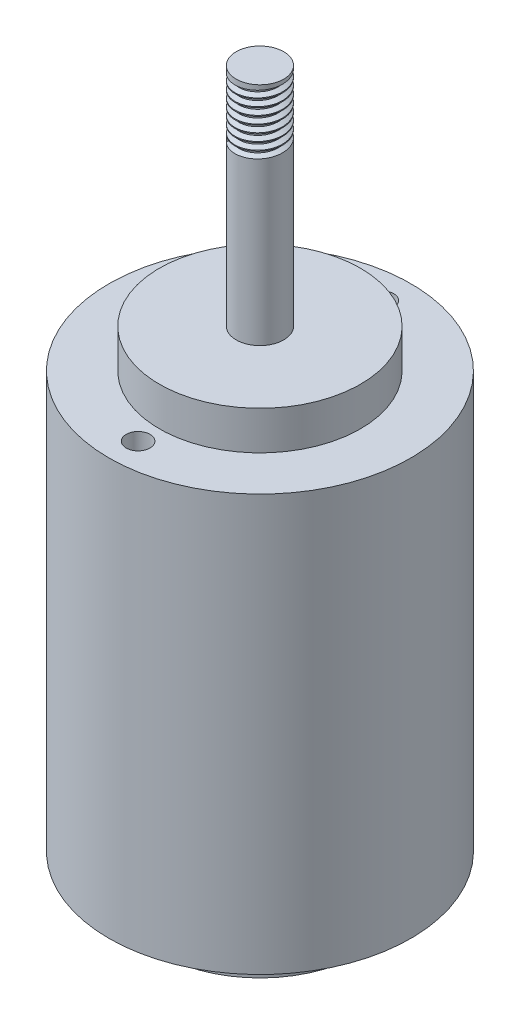
SolidWorks part; units mm, degrees
ref_plane "Front Plane" through (0, 0, 0) normal (0, 0, 1) x (1, 0, 0)
ref_plane "Top Plane" through (0, 0, 0) normal (0, 1, 0) x (1, 0, 0)
ref_plane "Right Plane" through (0, 0, 0) normal (1, 0, 0) x (0, 0, -1)
sketch "Sketch1" plane through (0, 0, 0) normal (0, 1, 0) x (1, 0, 0)
  circle A0 centre (0, 0) radius 25.4
  dimension "D1" = 50.8
extrude "Boss-Extrude1" add sketch "Sketch1" along normal blind 70
sketch "Sketch2" plane through (0, 70, 0) normal (0, 1, 0) x (1, 0, 0)
  circle A0 centre (0, 0) radius 16.9161
extrude "Boss-Extrude2" add sketch "Sketch2" along normal blind 6.5
sketch "Sketch3" plane through (0, 76.5, 0) normal (0, 1, 0) x (1, 0, 0)
  circle A0 centre (0, 0) radius 4
  dimension "D1" = 8
extrude "Boss-Extrude3" add sketch "Sketch3" along normal blind 38
sketch "Sketch4" plane through (0, 70, 0) normal (0, 1, 0) x (1, 0, 0)
  circle A0 centre (0, 20.5) radius 2
  circle A1 centre (0, -20.5) radius 2
  dimension "D1" = 4
  dimension "D2" = 41
  dimension "D3" = 20.5
extrude "Cut-Extrude1" cut sketch "Sketch4" against normal blind 12.7
ref_plane "Plane1" through (0, 35, 0) normal (0, 1, 0) x (1, 0, 0)
mirror "Mirror1" about plane through (0, 35, 0) normal (0, 1, 0) of "Boss-Extrude2"
thread "Thread1" pitch 1.27 method cut profile "Thread Profile1" start angle 0, offset 0, length 10, pitch 1.27, diameter 8
ref_plane "Plane2" through (-4, 114.5, 0) normal (0, 0, 1) x (-1, 0, 0)
sketch "Thread Profile1" plane through (-4, 114.5, 0) normal (0, 0, 1) x (-1, 0, 0)
  line L0 (0, 0) -> (0, 1.27) construction
  line L11 (0, 0) -> (0, 1.1112)
  line L12 (0, 1.1112) -> (-0.6874, 0.7144)
  line L13 (-0.6874, 0.7144) -> (-0.6874, 0.3969)
  line L15 (-0.6874, 0.3969) -> (0, 0)
  line L17 (-0.6874, 0.5556) -> (0, 0.5556) construction
  point P2 (0, 0)
  dimension "Pitch" = 1.27
  dimension "Profile_Angle" = 60
  dimension "Profile_Land" = 0.3175
  dimension "Profile_Height" = 0.6874
